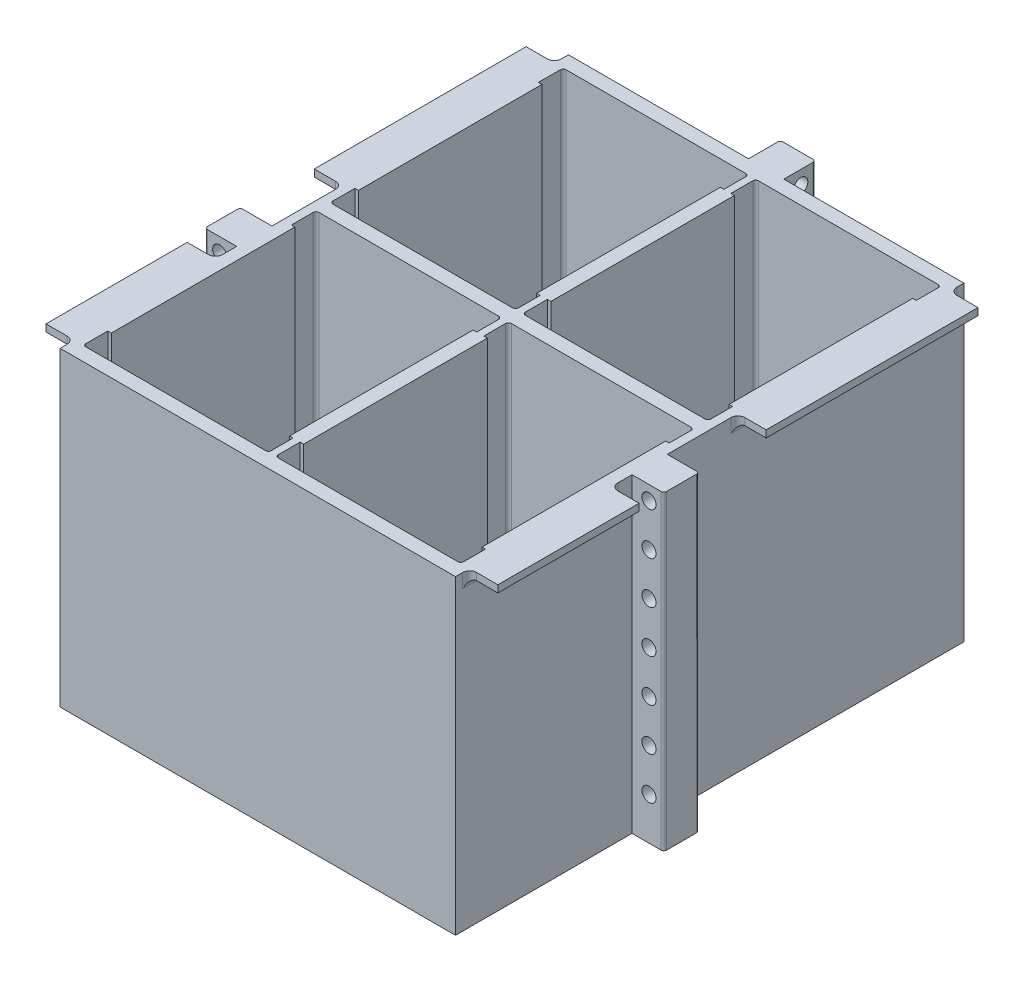
SolidWorks part; units mm, degrees
material "6061 Alloy"
ref_plane "Front Plane" through (0, 0, 0) normal (0, 0, 1) x (1, 0, 0)
ref_plane "Top Plane" through (0, 0, 0) normal (0, 1, 0) x (1, 0, 0)
ref_plane "Right Plane" through (0, 0, 0) normal (1, 0, 0) x (0, 0, -1)
sketch "Sketch1" plane through (0, 0, 0) normal (0, 1, 0) x (1, 0, 0)
  line L0 (-31.75, -228.6) -> (31.75, -228.6) construction
  line L1 (177.8, 228.6) -> (-177.8, 228.6) construction
  line L2 (177.8, 228.6) -> (177.8, -228.6) construction
  line L3 (177.8, -228.6) -> (-177.8, -228.6) construction
  line L4 (-177.8, 228.6) -> (-177.8, -228.6) construction
  line L5 (177.8, 228.6) -> (-177.8, -228.6) construction
  line L6 (177.8, -228.6) -> (-177.8, 228.6) construction
  line L7 (-31.75, -228.6) -> (-31.75, -269.875) construction
  line L8 (31.75, -228.6) -> (31.75, -269.875) construction
  line L9 (-31.75, -269.875) -> (31.75, -269.875) construction
  line L10 (-177.8, -228.6) -> (-31.75, -228.6)
  line L11 (31.75, -228.6) -> (-31.75, -228.6)
  line L12 (15.875, 228.6) -> (-15.875, 228.6) construction
  line L13 (15.875, 228.6) -> (15.875, 257.175)
  line L14 (31.75, -228.6) -> (177.8, -228.6)
  line L15 (-15.875, 228.6) -> (-15.875, 257.175)
  line L16 (15.875, 257.175) -> (-15.875, 257.175)
  line L17 (-15.875, 228.6) -> (-177.8, 228.6)
  line L18 (15.875, 228.6) -> (177.8, 228.6)
  line L19 (-177.8, -38.1) -> (-206.375, -38.1)
  line L20 (-177.8, -38.1) -> (-177.8, -69.85) construction
  line L21 (-206.375, -38.1) -> (-206.375, -69.85)
  line L22 (-177.8, -69.85) -> (-206.375, -69.85)
  line L23 (177.8, -38.1) -> (177.8, -69.85) construction
  line L24 (177.8, -38.1) -> (206.375, -38.1)
  line L25 (177.8, -69.85) -> (206.375, -69.85)
  line L26 (206.375, -38.1) -> (206.375, -69.85)
  line L27 (-177.8, 228.6) -> (-177.8, -38.1)
  line L28 (-177.8, -69.85) -> (-177.8, -228.6)
  line L29 (177.8, -69.85) -> (177.8, -228.6)
  line L30 (177.8, -38.1) -> (177.8, 228.6)
  point P0 (0, 0)
  point P6 (192.0875, -38.1)
  point P13 (0, 228.6)
  point P22 (192.0875, -69.85)
  point P25 (-192.0875, -69.85)
  dimension "D1" = 355.6
  dimension "D2" = 457.2
  dimension "D3" = 146.05
  dimension "D4" = 146.05
  dimension "D5" = 41.275
  dimension "D6" = 161.925
  dimension "D7" = 31.75
  dimension "D8" = 28.575
  dimension "D9" = 266.7
  dimension "D10" = 266.7
  dimension "D11" = 31.75
  dimension "D12" = 31.75
  dimension "D13" = 28.575
  dimension "D14" = 28.575
extrude "Boss-Extrude1" add sketch "Sketch1" along normal blind 279.4
ref_point "Point2"
ref_axis "Axis1" through (0, 139.7, 228.6) along (0, 1, 0)
sketch "Sketch2" plane through (0, 0, 69.85) normal (0, 0, 1) x (1, 0, 0)
  line L0 (-193.04, 279.4) -> (-193.04, 0) construction
  line L1 (-206.375, 279.4) -> (-177.8, 279.4) construction
  line L2 (-206.375, 0) -> (-177.8, 0) construction
  line L3 (-177.8, 279.4) -> (-177.8, 0) construction
  line L4 (0, 135.6782) -> (0, 345.0284)
  line L5 (0, 139.7) -> (0, 350.0578) construction
  line L6 (193.04, 279.4) -> (193.04, 0) construction
  circle A0 centre (-193.04, 38.1) radius 6.35
  circle A1 centre (-193.04, 76.2) radius 6.35
  circle A2 centre (-193.04, 114.3) radius 6.35
  circle A3 centre (-193.04, 152.4) radius 6.35
  circle A4 centre (-193.04, 190.5) radius 6.35
  circle A5 centre (-193.04, 228.6) radius 6.35
  circle A6 centre (-193.04, 266.7) radius 6.35
  circle A7 centre (193.04, 266.7) radius 6.35
  circle A8 centre (193.04, 228.6) radius 6.35
  circle A9 centre (193.04, 190.5) radius 6.35
  circle A10 centre (193.04, 152.4) radius 6.35
  circle A11 centre (193.04, 114.3) radius 6.35
  circle A12 centre (193.04, 76.2) radius 6.35
  circle A13 centre (193.04, 38.1) radius 6.35
  point P10 (-193.04, 53.7554)
  point P45 (193.04, 53.7554)
  dimension "D2" = 12.7
  dimension "D1" = 15.24
  dimension "D3" = 38.1
  dimension "D4" = 7
extrude "Cut-Extrude1" cut sketch "Sketch2" against normal blind 45.72 contours A6 | A5 | A3 | A4 | A2 | A1 | A0 | A7 | A8 | A9 | A10 | A11 | A12 | A13
sketch "Sketch3" plane through (-15.875, 0, 0) normal (-1, 0, 0) x (0, 0, 1)
  line L0 (-243.84, 279.4) -> (-243.84, 0) construction
  line L1 (-257.175, 279.4) -> (-228.6, 279.4) construction
  line L2 (-257.175, 0) -> (-228.6, 0) construction
  line L3 (-228.6, 279.4) -> (-228.6, 0) construction
  circle A0 centre (-243.84, 38.1) radius 6.35
  circle A1 centre (-243.84, 76.2) radius 6.35
  circle A2 centre (-243.84, 114.3) radius 6.35
  circle A3 centre (-243.84, 152.4) radius 6.35
  circle A4 centre (-243.84, 190.5) radius 6.35
  circle A5 centre (-243.84, 228.6) radius 6.35
  circle A6 centre (-243.84, 266.7) radius 6.35
  point P10 (-243.84, 53.0999)
  dimension "D2" = 12.7
  dimension "D1" = 15.24
  dimension "D3" = 38.1
  dimension "D4" = 7
extrude "Cut-Extrude2" cut sketch "Sketch3" against normal blind 45.72
fillet "Fillet1" radius 2.54 6 edges at (206.375, 139.7, 69.85) (206.375, 139.7, 38.1) (15.875, 139.7, -257.175) (-15.875, 139.7, -257.175) (-206.375, 139.7, 69.85) (-206.375, 139.7, 38.1)
sketch "Sketch4" plane through (0, 279.4, 0) normal (0, 1, 0) x (1, 0, 0)
  line L0 (177.8, 215.9) -> (-177.8, 215.9) construction
  line L1 (177.8, -228.6) -> (-177.8, -228.6) construction
  line L2 (177.8, -228.6) -> (177.8, 228.6) construction
  line L3 (177.8, 228.6) -> (-177.8, 228.6) construction
  line L4 (-177.8, -228.6) -> (-177.8, 228.6) construction
  line L5 (177.8, -228.6) -> (-177.8, 228.6) construction
  line L6 (177.8, 228.6) -> (-177.8, -228.6) construction
  line L7 (0, 0) -> (-177.8, 0) construction
  line L8 (0, 0) -> (0, 215.9) construction
  line L9 (-177.8, -6.35) -> (177.8, -6.35) construction
  line L10 (-177.8, -6.35) -> (-177.8, 6.35) construction
  line L11 (-177.8, 6.35) -> (177.8, 6.35) construction
  line L12 (177.8, -6.35) -> (177.8, 6.35) construction
  line L13 (-177.8, -6.35) -> (177.8, 6.35) construction
  line L14 (-177.8, 6.35) -> (177.8, -6.35) construction
  line L15 (-3.175, 215.9) -> (-3.175, 6.35) construction
  line L16 (-169.8625, 215.9) -> (-169.8625, 6.35) construction
  line L17 (-169.8625, 215.9) -> (-3.175, 215.9) construction
  line L18 (-169.8625, 215.9) -> (-169.8625, 193.675) construction
  line L19 (-3.175, 215.9) -> (-3.175, 193.675) construction
  line L20 (-169.8625, 193.675) -> (-3.175, 193.675) construction
  line L21 (-3.175, 6.35) -> (-169.8625, 6.35) construction
  line L22 (-3.175, 6.35) -> (-3.175, 28.575) construction
  line L23 (-169.8625, 6.35) -> (-169.8625, 28.575) construction
  line L24 (-3.175, 28.575) -> (-169.8625, 28.575) construction
  line L25 (-6.35, 28.575) -> (-6.35, 193.675) construction
  line L26 (-166.6875, 28.575) -> (-166.6875, 193.675) construction
  line L27 (-3.175, 215.9) -> (-169.8625, 215.9)
  line L28 (-169.8625, 215.9) -> (-169.8625, 193.675)
  line L29 (-169.8625, 193.675) -> (-166.6875, 193.675)
  line L30 (-166.6875, 193.675) -> (-166.6875, 28.575)
  line L31 (-166.6875, 28.575) -> (-169.8625, 28.575)
  line L32 (-169.8625, 28.575) -> (-169.8625, 6.35)
  line L33 (-169.8625, 6.35) -> (-3.175, 6.35)
  line L34 (-3.175, 6.35) -> (-3.175, 28.575)
  line L35 (-3.175, 28.575) -> (-6.35, 28.575)
  line L36 (-6.35, 28.575) -> (-6.35, 193.675)
  line L37 (-6.35, 193.675) -> (-3.175, 193.675)
  line L38 (-3.175, 193.675) -> (-3.175, 215.9)
  line L39 (3.175, 28.575) -> (6.35, 28.575)
  line L40 (3.175, 6.35) -> (3.175, 28.575)
  line L41 (169.8625, 6.35) -> (3.175, 6.35)
  line L42 (169.8625, 28.575) -> (169.8625, 6.35)
  line L43 (166.6875, 28.575) -> (169.8625, 28.575)
  line L44 (166.6875, 193.675) -> (166.6875, 28.575)
  line L45 (169.8625, 193.675) -> (166.6875, 193.675)
  line L46 (6.35, 28.575) -> (6.35, 193.675)
  line L47 (6.35, 193.675) -> (3.175, 193.675)
  line L48 (169.8625, 215.9) -> (169.8625, 193.675)
  line L49 (3.175, 215.9) -> (169.8625, 215.9)
  line L50 (3.175, 193.675) -> (3.175, 215.9)
  line L51 (-166.6875, -28.575) -> (-166.6875, -193.675) construction
  line L52 (-6.35, -28.575) -> (-6.35, -193.675) construction
  line L53 (-3.175, -28.575) -> (-169.8625, -28.575) construction
  line L54 (-169.8625, -6.35) -> (-169.8625, -28.575) construction
  line L55 (-3.175, -6.35) -> (-3.175, -28.575) construction
  line L56 (-3.175, -6.35) -> (-169.8625, -6.35) construction
  line L57 (-169.8625, -193.675) -> (-3.175, -193.675) construction
  line L58 (-3.175, -215.9) -> (-3.175, -193.675) construction
  line L59 (-169.8625, -215.9) -> (-169.8625, -193.675) construction
  line L60 (-169.8625, -215.9) -> (-3.175, -215.9) construction
  line L61 (-169.8625, -215.9) -> (-169.8625, -6.35) construction
  line L62 (-3.175, -215.9) -> (-3.175, -6.35) construction
  line L63 (-177.8, -6.35) -> (177.8, -6.35) construction
  line L64 (177.8, -215.9) -> (-177.8, -215.9) construction
  line L65 (3.175, -193.675) -> (3.175, -215.9)
  line L66 (3.175, -215.9) -> (169.8625, -215.9)
  line L67 (169.8625, -215.9) -> (169.8625, -193.675)
  line L68 (6.35, -193.675) -> (3.175, -193.675)
  line L69 (6.35, -28.575) -> (6.35, -193.675)
  line L70 (169.8625, -193.675) -> (166.6875, -193.675)
  line L71 (166.6875, -193.675) -> (166.6875, -28.575)
  line L72 (166.6875, -28.575) -> (169.8625, -28.575)
  line L73 (169.8625, -28.575) -> (169.8625, -6.35)
  line L74 (169.8625, -6.35) -> (3.175, -6.35)
  line L75 (3.175, -6.35) -> (3.175, -28.575)
  line L76 (3.175, -28.575) -> (6.35, -28.575)
  line L77 (-3.175, -193.675) -> (-3.175, -215.9)
  line L78 (-6.35, -193.675) -> (-3.175, -193.675)
  line L79 (-6.35, -28.575) -> (-6.35, -193.675)
  line L80 (-3.175, -28.575) -> (-6.35, -28.575)
  line L81 (-3.175, -6.35) -> (-3.175, -28.575)
  line L82 (-169.8625, -6.35) -> (-3.175, -6.35)
  line L83 (-169.8625, -28.575) -> (-169.8625, -6.35)
  line L84 (-166.6875, -28.575) -> (-169.8625, -28.575)
  line L85 (-166.6875, -193.675) -> (-166.6875, -28.575)
  line L86 (-169.8625, -193.675) -> (-166.6875, -193.675)
  line L87 (-169.8625, -215.9) -> (-169.8625, -193.675)
  line L88 (-3.175, -215.9) -> (-169.8625, -215.9)
  point P0 (0, 0)
  point P29 (-4.7625, 28.575)
  point P30 (4.7625, 28.575)
  point P68 (4.7625, -28.575)
  dimension "D1" = 12.7
  dimension "D2" = 12.7
  dimension "D3" = 3.175
  dimension "D4" = 7.9375
  dimension "D5" = 22.225
  dimension "D6" = 22.225
  dimension "D7" = 3.175
  dimension "D8" = 3.175
extrude "Cut-Extrude3" cut sketch "Sketch4" against normal blind 274.32
fillet "Fillet2" radius 2.54 16 edges at (169.8625, 142.24, 215.9) (-3.175, 142.24, 215.9) (-169.8625, 142.24, 215.9) (3.175, 142.24, 215.9) (169.8625, 142.24, 6.35) (-3.175, 142.24, 6.35) (-169.8625, 142.24, 6.35) (3.175, 142.24, 6.35) (-3.175, 142.24, -6.35) (-169.8625, 142.24, -6.35) (-3.175, 142.24, -215.9) (-169.8625, 142.24, -215.9) (3.175, 142.24, -215.9) (169.8625, 142.24, -215.9) (169.8625, 142.24, -6.35) (3.175, 142.24, -6.35)
sketch "Sketch6" plane through (177.8, 0, 0) normal (1, 0, 0) x (0, 0, -1)
  line L0 (-215.9, 279.4) -> (-215.9, 273.05)
  line L1 (-215.9, 279.4) -> (-88.9, 279.4)
  line L2 (-215.9, 273.05) -> (-88.9, 273.05)
  line L3 (-88.9, 279.4) -> (-88.9, 273.05)
  line L4 (-228.6, 279.4) -> (-228.6, 0) construction
  point P0 (0, 0)
  dimension "D1" = 127
  dimension "D2" = 6.35
  dimension "D3" = 12.7
extrude "Boss-Extrude2" add sketch "Sketch6" along normal blind 25.4
mirror "Mirror1" about plane through (0, 0, 0) normal (1, 0, 0) of "Boss-Extrude2"
sketch "Sketch8" plane through (177.8, 0, 0) normal (1, 0, 0) x (0, 0, -1)
  line L0 (215.9, 279.4) -> (215.9, 273.05)
  line L1 (215.9, 279.4) -> (25.4, 279.4)
  line L2 (215.9, 273.05) -> (25.4, 273.05)
  line L3 (25.4, 279.4) -> (25.4, 273.05)
  line L5 (228.6, 279.4) -> (228.6, 0) construction
  point P0 (0, 0)
  point P7 (215.9, 276.225)
  dimension "D1" = 6.35
  dimension "D2" = 190.5
  dimension "D3" = 12.7
extrude "Boss-Extrude3" add sketch "Sketch8" along normal blind 25.4
mirror "Mirror2" about plane through (0, 0, 0) normal (1, 0, 0) of "Boss-Extrude3"
fillet "Fillet3" radius 6.35 12 edges at (-177.8, 276.225, 88.9) (-177.8, 273.05, 152.4) (-177.8, 276.225, 215.9) (-177.8, 276.225, -25.4) (-177.8, 273.05, -120.65) (-177.8, 276.225, -215.9) (177.8, 276.225, -215.9) (177.8, 273.05, -120.65) (177.8, 276.225, -25.4) (177.8, 276.225, 88.9) (177.8, 276.225, 215.9) (177.8, 273.05, 152.4)
